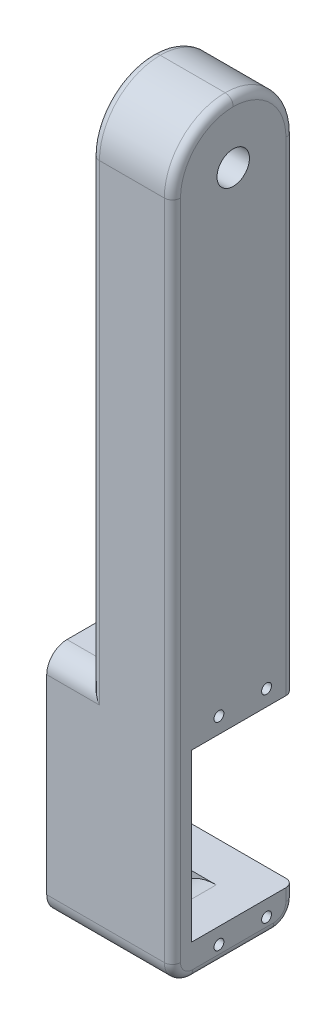
SolidWorks part; units mm, degrees
material "ABS"
ref_plane "Front" through (0, 0, 0) normal (0, 0, 1) x (1, 0, 0)
ref_plane "Top" through (0, 0, 0) normal (0, 1, 0) x (1, 0, 0)
ref_plane "Right" through (0, 0, 0) normal (1, 0, 0) x (0, 0, -1)
sketch "Sketch1" plane through (0, 0, 0) normal (0, 1, 0) x (1, 0, 0)
  line L1 (-10, -15) -> (10, -15)
  line L2 (-10, -15) -> (-10, 15)
  line L3 (-10, 15) -> (10, 15)
  line L4 (10, -15) -> (10, 15)
  point P4 (0, -15)
  point P6 (-10, 0)
  dimension "D1" = 30
  dimension "D2" = 20
extrude "Boss-Extrude1" add sketch "Sketch1" along normal blind 183.3
sketch "Sketch13" plane through (-10, 0, 0) normal (-1, 0, 0) x (0, 0, 1)
  line L0 (15, 183.3) -> (15, 0) construction
  line L1 (-15, 0) -> (15, 0)
  line L2 (-15, 0) -> (-15, 57)
  line L3 (-15, 57) -> (15, 57)
  line L4 (15, 0) -> (15, 57)
  dimension "D1" = 57
extrude "Boss-Extrude2" add sketch "Sketch13" along normal blind 11
sketch "Sketch3" plane through (10, 0, 0) normal (1, 0, 0) x (0, 0, -1)
  line L0 (-15, 0) -> (15, 0) construction
  line L1 (-10.3, 8) -> (10.3, 8)
  line L2 (-10.3, 8) -> (-10.3, 49)
  line L3 (-10.3, 49) -> (10.3, 49)
  line L4 (10.3, 8) -> (10.3, 49)
  point P4 (0, 8)
  point P7 (0, 0)
  dimension "D1" = 20.6
  dimension "D2" = 41
  dimension "D3" = 8
extrude "Cut-Extrude1" cut sketch "Sketch3" against normal blind 40
sketch "Sketch11" plane through (-10, 0, 0) normal (-1, 0, 0) x (0, 0, 1)
  line L0 (0, 183.3) -> (0, 168.3) construction
  line L1 (-15, 183.3) -> (15, 183.3) construction
  line L2 (0, 168.3) -> (15, 168.3) construction
  line L3 (15, 183.3) -> (15, 57) construction
  circle A0 centre (0, 168.3) radius 10.5
  dimension "D1" = 21
extrude "Cut-Extrude4" cut sketch "Sketch11" against normal blind 2.4
sketch "Sketch12" plane through (-7.6, 0, 0) normal (-1, 0, 0) x (0, 0, 1)
  circle A0 centre (0, 168.3) radius 4
  dimension "D1" = 8
extrude "Cut-Extrude5" cut sketch "Sketch12" against normal through all
sketch "Sketch14" plane through (0, 0, -15) normal (0, 0, -1) x (-1, 0, 0)
  line L0 (-10, 183.3) -> (-10, 0) construction
  line L1 (-10, 8) -> (21, 8)
  line L2 (-10, 8) -> (-10, 49)
  line L3 (-10, 49) -> (21, 49)
  line L4 (21, 8) -> (21, 49)
  line L5 (21, 57) -> (21, 0) construction
extrude "Cut-Extrude6" cut sketch "Sketch14" against normal up to surface (25.3 mm away) up to face at (-5.5, 28.5, 10.3)
hole_wizard "#2 Clearance Hole2" positions "Sketch16" profile "Sketch17" hole size "#2" standard "ANSI Inch"
sketch "Sketch16" plane through (-21, 0, 0) normal (-1, 0, 0) x (0, 0, 1)
  line L0 (-9.5, 5) -> (7.5, 5) construction
  line L1 (7.5, 5) -> (7.5, 52) construction
  line L2 (7.5, 52) -> (-9.5, 52) construction
  line L3 (-9.5, 52) -> (-9.5, 5) construction
  line L5 (10.3, 49) -> (10.3, 8) construction
  line L7 (15, 0) -> (15, 57) construction
  point P0 (-9.5, 5)
  point P2 (7.5, 5)
  point P4 (-9.5, 52)
  point P6 (7.5, 52)
  point P20 (10.3, 28.5)
  point P21 (7.5, 28.5)
  dimension "D1" = 47
  dimension "D2" = 17
  dimension "D3" = 7.5
sketch "Sketch17" plane through (-21, 5, -9.5) normal (0, 1, 0) x (0, 0, 1)
  line L0 (0, 0) -> (0, 7.0826)
  line L1 (0, 7.0826) -> (1.2192, 6.35)
  line L2 (1.2192, 6.35) -> (1.2192, 0)
  line L5 (1.2192, 0) -> (0, 0)
  line L10 (0, 7.0826) -> (-1.2192, 6.35) construction
  line L11 (0, -6.35) -> (0, 107.95) construction
  dimension "Hole Dia." = 2.4384
  dimension "Hole Depth" = 6.35
  dimension "Drill Angle" = 118
sketch "Sketch18" plane through (-21, 0, 0) normal (-1, 0, 0) x (0, 0, 1)
  line L1 (-12.329, 5) -> (-10.9145, 2.55)
  line L2 (-10.9145, 2.55) -> (-8.0855, 2.55)
  line L3 (-8.0855, 2.55) -> (-6.671, 5)
  line L4 (-6.671, 5) -> (-8.0855, 7.45)
  line L5 (-8.0855, 7.45) -> (-10.9145, 7.45)
  line L6 (-10.9145, 7.45) -> (-12.329, 5)
  line L7 (10.329, 5) -> (8.9145, 7.45)
  line L8 (8.9145, 7.45) -> (6.0855, 7.45)
  line L9 (6.0855, 7.45) -> (4.671, 5)
  line L10 (4.671, 5) -> (6.0855, 2.55)
  line L11 (6.0855, 2.55) -> (8.9145, 2.55)
  line L12 (8.9145, 2.55) -> (10.329, 5)
  line L13 (4.671, 52) -> (6.0855, 49.55)
  line L14 (6.0855, 49.55) -> (8.9145, 49.55)
  line L15 (8.9145, 49.55) -> (10.329, 52)
  line L16 (10.329, 52) -> (8.9145, 54.45)
  line L17 (8.9145, 54.45) -> (6.0855, 54.45)
  line L18 (6.0855, 54.45) -> (4.671, 52)
  line L19 (-6.671, 52) -> (-8.0855, 54.45)
  line L20 (-8.0855, 54.45) -> (-10.9145, 54.45)
  line L21 (-10.9145, 54.45) -> (-12.329, 52)
  line L22 (-12.329, 52) -> (-10.9145, 49.55)
  line L23 (-10.9145, 49.55) -> (-8.0855, 49.55)
  line L24 (-8.0855, 49.55) -> (-6.671, 52)
  circle A0 centre (-9.5, 5) radius 2.45 construction
  circle A1 centre (7.5, 5) radius 2.45 construction
  circle A2 centre (7.5, 52) radius 2.45 construction
  circle A3 centre (-9.5, 52) radius 2.45 construction
  dimension "D1" = 4.9
extrude "Cut-Extrude8" cut sketch "Sketch18" against normal blind 1.6 from offset 2 offset against normal yes
hole_wizard "#2 Clearance Hole3" positions "Sketch19" profile "Sketch20" hole size "#2" standard "ANSI Inch"
sketch "Sketch19" plane through (10, 0, 0) normal (1, 0, 0) x (0, 0, -1)
  line L0 (8.22, 4.1) -> (-3.52, 4.1) construction
  line L1 (-3.52, 4.1) -> (-3.52, 52.9) construction
  line L2 (-3.52, 52.9) -> (8.22, 52.9) construction
  line L3 (8.22, 52.9) -> (8.22, 4.1) construction
  line L5 (-10.3, 8) -> (15, 8) construction
  line L6 (-10.3, 49) -> (-10.3, 8) construction
  point P0 (8.22, 4.1)
  point P2 (-3.52, 4.1)
  point P4 (-3.52, 52.9)
  point P6 (8.22, 52.9)
  point P18 (2.35, 4.1)
  point P21 (2.35, 8)
  point P22 (-3.52, 28.5)
  point P25 (-10.3, 28.5)
  dimension "D1" = 48.8
  dimension "D2" = 11.74
sketch "Sketch20" plane through (10, 4.1, -8.22) normal (0, 1, 0) x (0, 0, -1)
  line L0 (0, 0) -> (0, 7.5692)
  line L1 (0, 7.5692) -> (1.2192, 6.35)
  line L2 (1.2192, 6.35) -> (1.2192, 0)
  line L5 (1.2192, 0) -> (0, 0)
  line L10 (0, 7.5692) -> (-1.2192, 6.35) construction
  line L11 (0, -6.35) -> (0, 107.95) construction
  dimension "Hole Dia." = 2.4384
  dimension "Hole Depth" = 6.35
  dimension "Drill Angle" = 90
fillet "Fillet3" radius 15 2 edges at (0, 183.3, -15) (0, 183.3, 15)
fillet "Fillet4" radius 5 4 edges at (-5.5, 0, -15) (-15.5, 57, -15) (-15.5, 57, 15) (-5.5, 0, 15)
fillet "Fillet5" radius 2 12 edges at (10, 108.65, -15) (10, 178.9066, -10.6066) (10, 178.9066, 10.6066) (10, 6.5, -15) (10, 1.4645, -13.5355) (10, 0, 0) (10, 1.4645, 13.5355) (-10, 110.15, -15) (-10, 178.9066, -10.6066) (-10, 178.9066, 10.6066) (10, 86.65, 15) (-10, 110.15, 15)
sketch "Sketch21" plane through (0, 0, 0) normal (0, -1, 0) x (1, 0, 0)
  line L0 (10, 10) -> (10, -10) construction
  line L1 (-10.5, 5) -> (-16.5, 5)
  line L2 (-10.5, 5) -> (-10.5, -5)
  line L3 (-10.5, -5) -> (-16.5, -5)
  line L4 (-16.5, 5) -> (-16.5, -5)
  point P4 (-10.5, 0)
  point P7 (10, 0)
  point P8 (-13.5, 5)
  dimension "D1" = 6
  dimension "D2" = 10
  dimension "D3" = 23.5
extrude "Cut-Extrude9" cut sketch "Sketch21" against normal up to surface (8 mm away) up to face at (-2.7172, 8, -4.5628)
fillet "Fillet6" radius 12 1 edges at (-10.5, 8, 0)
fillet "Fillet7" radius 6 1 edges at (-13.5, 0, 5)
sketch "Sketch22" plane through (10, 0, 0) normal (1, 0, 0) x (0, 0, -1)
  line L0 (-10.3, 8) -> (13, 8) construction
  line L1 (-6.349, 52.9) -> (-4.9345, 50.45)
  line L2 (-4.9345, 50.45) -> (-2.1055, 50.45)
  line L3 (-2.1055, 50.45) -> (-0.691, 52.9)
  line L4 (-0.691, 52.9) -> (-2.1055, 55.35)
  line L5 (-2.1055, 55.35) -> (-4.9345, 55.35)
  line L6 (-4.9345, 55.35) -> (-6.349, 52.9)
  line L7 (5.391, 52.9) -> (6.8055, 50.45)
  line L8 (6.8055, 50.45) -> (9.6345, 50.45)
  line L9 (9.6345, 50.45) -> (11.049, 52.9)
  line L10 (11.049, 52.9) -> (9.6345, 55.35)
  line L11 (9.6345, 55.35) -> (6.8055, 55.35)
  line L12 (6.8055, 55.35) -> (5.391, 52.9)
  line L13 (-6.349, 4.1) -> (-4.9345, 1.65)
  line L14 (-4.9345, 1.65) -> (-2.1055, 1.65)
  line L15 (-2.1055, 1.65) -> (-0.691, 4.1)
  line L16 (-0.691, 4.1) -> (-2.1055, 6.55)
  line L17 (-2.1055, 6.55) -> (-4.9345, 6.55)
  line L18 (-4.9345, 6.55) -> (-6.349, 4.1)
  line L19 (5.391, 4.1) -> (6.8055, 1.65)
  line L20 (6.8055, 1.65) -> (9.6345, 1.65)
  line L21 (9.6345, 1.65) -> (11.049, 4.1)
  line L22 (11.049, 4.1) -> (9.6345, 6.55)
  line L23 (9.6345, 6.55) -> (6.8055, 6.55)
  line L24 (6.8055, 6.55) -> (5.391, 4.1)
  circle A0 centre (-3.52, 52.9) radius 2.45 construction
  circle A1 centre (8.22, 52.9) radius 2.45 construction
  circle A2 centre (-3.52, 4.1) radius 2.45 construction
  circle A3 centre (8.22, 4.1) radius 2.45 construction
  dimension "D1" = 4.9
extrude "Cut-Extrude10" cut sketch "Sketch22" against normal blind 1.8 from offset 2 offset against normal yes
